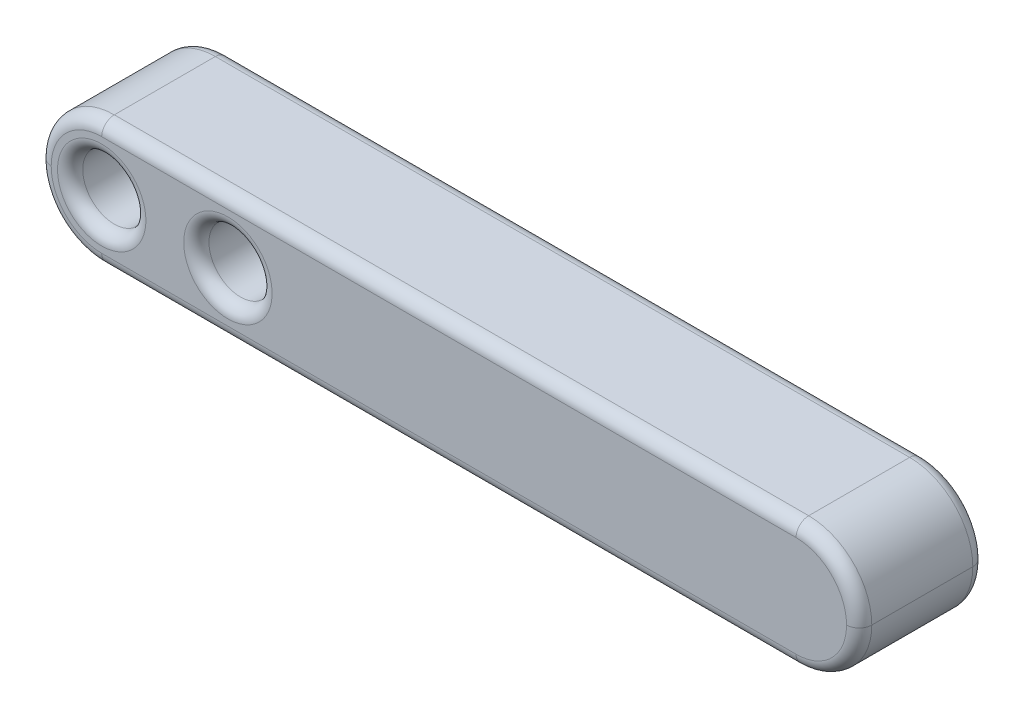
SolidWorks part; units mm, degrees
ref_plane "Front Plane" through (0, 0, 0) normal (0, 0, 1) x (1, 0, 0)
ref_plane "Top Plane" through (0, 0, 0) normal (0, 1, 0) x (1, 0, 0)
ref_plane "Right Plane" through (0, 0, 0) normal (1, 0, 0) x (0, 0, -1)
sketch "Sketch1" plane through (0, 0, 0) normal (0, 0, 1) x (1, 0, 0)
  line L1 (-32.5, -5) -> (32.5, -5)
  line L2 (-32.5, -5) -> (-32.5, 5)
  line L3 (-32.5, 5) -> (32.5, 5)
  line L4 (32.5, -5) -> (32.5, 5)
  line L5 (-32.5, -5) -> (32.5, 5) construction
  line L6 (-32.5, 5) -> (32.5, -5) construction
  circle A0 centre (-27.5, 0) radius 2.5
  circle A1 centre (-17.5, 0) radius 2.5
  point P0 (0, 0)
  dimension "D3" = 5
  dimension "D1" = 65
  dimension "D2" = 10
  dimension "D4" = 5
  dimension "D5" = 10
extrude "Boss-Extrude1" add sketch "Sketch1" along normal blind 10
fillet "Fillet1" radius 5 4 edges at (32.5, -5, 5) (32.5, 5, 5) (-32.5, 5, 5) (-32.5, -5, 5)
fillet "Fillet2" radius 1 16 edges at (31.0355, 3.5355, 0) (0, 5, 0) (-15, 0, 0) (-15, 0, 10) (-25, 0, 0) (-25, 0, 10) (0, -5, 0) (0, 5, 10) (0, -5, 10) (-31.0355, -3.5355, 0) (-31.0355, 3.5355, 0) (31.0355, -3.5355, 0) (-31.0355, -3.5355, 10) (-31.0355, 3.5355, 10) (31.0355, 3.5355, 10) (31.0355, -3.5355, 10)
